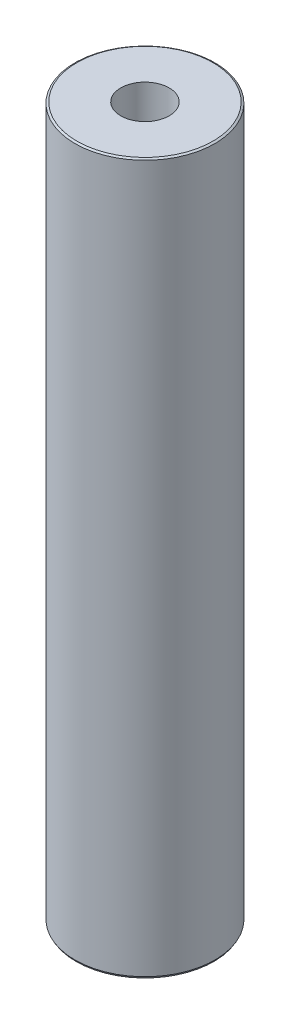
SolidWorks part; units mm, degrees
ref_plane "Front Plane" through (0, 0, 0) normal (0, 0, 1) x (1, 0, 0)
ref_plane "Top Plane" through (0, 0, 0) normal (0, 1, 0) x (1, 0, 0)
ref_plane "Right Plane" through (0, 0, 0) normal (1, 0, 0) x (0, 0, -1)
sketch "Sketch1" plane through (0, 0, 0) normal (0, 1, 0) x (1, 0, 0)
  circle A0 centre (0, 0) radius 52.5
  dimension "SHAFT_OD" = 105
extrude "Boss-Extrude1" add sketch "Sketch1" along normal blind 532.5521
sketch "Sketch2" plane through (0, 0, 0) normal (0, 1, 0) x (1, 0, 0)
  circle A0 centre (0, 0) radius 18.1718
  dimension "BORE_D" = 36.3436
extrude "Cut-Extrude1" cut sketch "Sketch2" along normal through all
chamfer "Chamfer1" distance 0.8382 angle 60 2 edges at (0, 532.5521, 52.5) (0, 0, 52.5) first distance on face at (0, 532.5521, 52.5) first distance on face at (0, 0, 18.1718)
